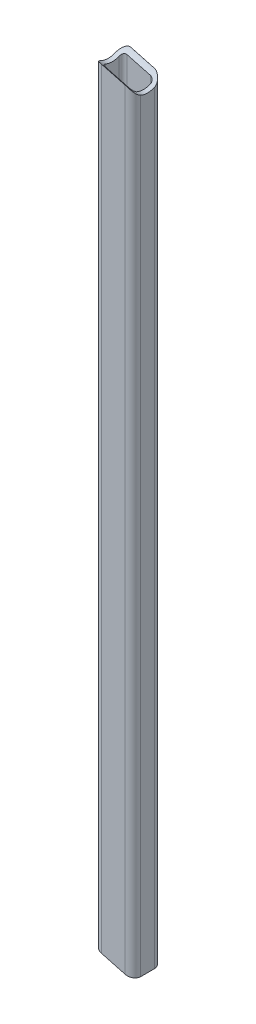
SolidWorks part; units mm, degrees
note: '?' marks a value the reader was unsure of.
material "Ст 3 ГОСТ 380-88"
ref_plane "Спереди" through (0, 0, 0) normal (0, 0, 1) x (1, 0, 0)
ref_plane "Сверху" through (0, 0, 0) normal (0, 1, 0) x (1, 0, 0)
ref_plane "Справа" through (0, 0, 0) normal (1, 0, 0) x (0, 0, -1)
ref_plane "Плоскость1" through (-10, 0, 0) normal (1, 0, 0) x (0, 0, -1)
ref_plane "Плоскость2" through (10, 0, 0) normal (1, 0, 0) x (0, 0, -1)
ref_plane "Плоскость3" through (0, 199, 0) normal (0, 1, 0) x (1, 0, 0)
ref_plane "Плоскость4" through (0, -200, 0) normal (0, 1, 0) x (1, 0, 0)
sketch "Эскиз1" plane through (0, 0, 0) normal (0, 1, 0) x (1, 0, 0)
  line L0 (-10, 7.5) -> (10, -7.5) construction
  line L1 (-6, 7.5) -> (6, 7.5)
  line L2 (-10, 3.5) -> (-10, -3.5)
  line L3 (-6, -7.5) -> (6, -7.5)
  line L4 (10, 3.5) -> (10, -3.5)
  line L5 (-10, -7.5) -> (10, 7.5) construction
  arc A0 (-10, -3.5) -> (-6, -7.5) centre (-6, -3.5) ccw
  arc A1 (6, -7.5) -> (10, -3.5) centre (6, -3.5) ccw
  arc A2 (6, 7.5) -> (10, 3.5) centre (6, 3.5) cw
  arc A3 (-6, 7.5) -> (-10, 3.5) centre (-6, 3.5) ccw
  point P4 (0, 0)
  dimension "D3" = 4
  dimension "D1" = 20
  dimension "D2" = 15
extrude "Вытянуть-Тонкостенный1" add sketch "Эскиз1" along normal up to surface (199 mm away) and the other way up to surface (200 mm away) thin up to plane "Плоскость3" other way up to plane "Плоскость4" thin type one direction reverse wall 2
ref_axis "Ось1" through (-10, 199, -22.5957) along (0, 0, 1)?
ref_plane "Плоскость5" through (49.0801, 183.1695, 0) normal (0.2588, 0.9659, 0) x (0, 0, 1)
ref_plane "Плоскость6" through (-59.0801, 15.8305, 0) normal (-0.9659, 0.2588, 0) x (0, 0, 1)
ref_point "Точка1"
sketch "Эскиз3" plane through (-59.0801, 15.8305, 0) normal (-0.9659, 0.2588, 0) x (0, 0, 1)
  line L0 (-22.5957, 189.631) -> (21.9553, 189.631) construction
  line L1 (0, -50) -> (0, 50) construction
  circle A1 centre (0, 194.631) radius 9
  dimension "D1" = 18
  dimension "D2" = 5
other "Сечение1" flip cut yes
extrude "Вырез-Вытянуть1" cut sketch "Эскиз3" against normal blind 30 and the other way blind 10 contours A1
ref_axis "Ось2" through (10, -200, 11.5479) along (0, 0, -1)?
ref_plane "Плоскость7" through (-49.3301, -184.1025, 0) normal (0.2588, 0.9659, 0) x (0, 0, -1)
other "Сечение2"
